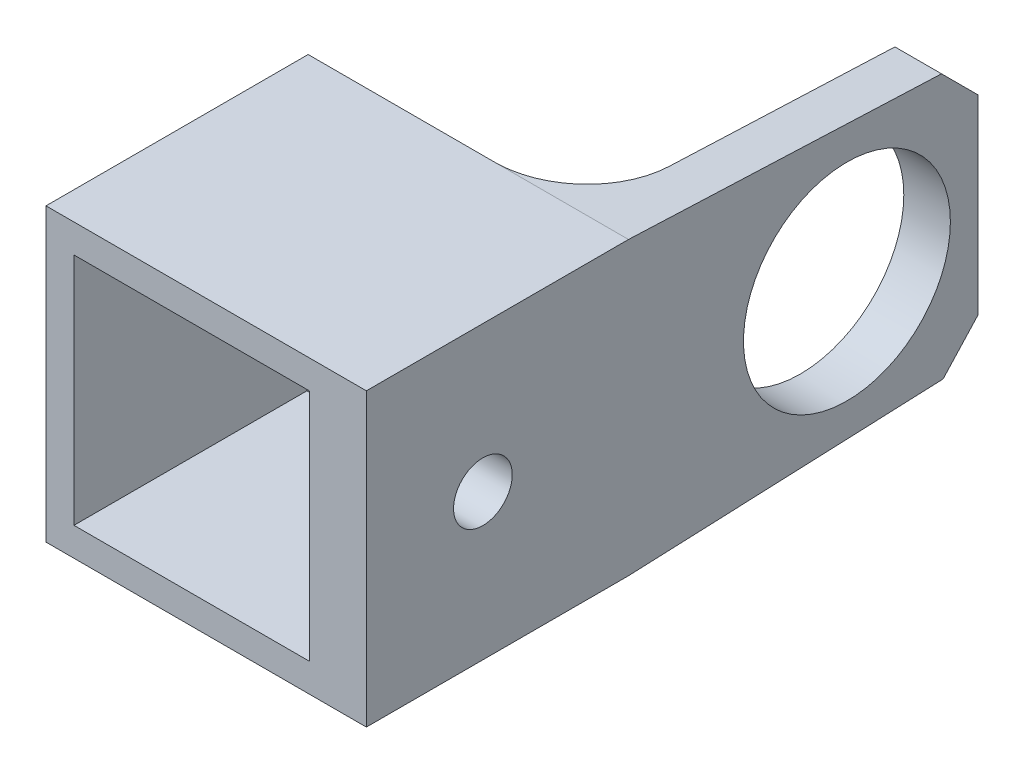
SolidWorks part; units mm, degrees
ref_plane "Front Plane" through (0, 0, 0) normal (0, 0, 1) x (1, 0, 0)
ref_plane "Top Plane" through (0, 0, 0) normal (0, 1, 0) x (1, 0, 0)
ref_plane "Right Plane" through (0, 0, 0) normal (1, 0, 0) x (0, 0, -1)
sketch "Sketch1" plane through (0, 0, 0) normal (0, 0, 1) x (1, 0, 0)
  line L1 (-15.875, -15.875) -> (15.875, -15.875)
  line L2 (-15.875, -15.875) -> (-15.875, 15.875)
  line L3 (-15.875, 15.875) -> (15.875, 15.875)
  line L4 (15.875, -15.875) -> (15.875, 15.875)
  line L5 (-15.875, -15.875) -> (15.875, 15.875) construction
  line L6 (-15.875, 15.875) -> (15.875, -15.875) construction
  point P0 (0, 0)
  dimension "D1" = 31.75
extrude "Boss-Extrude1" add sketch "Sketch1" along normal blind 28.575
sketch "Sketch2" plane through (0, 0, 28.575) normal (0, 0, 1) x (1, 0, 0)
  line L1 (-12.827, -12.7635) -> (12.827, -12.7635)
  line L2 (-12.827, -12.7635) -> (-12.827, 12.7635)
  line L3 (-12.827, 12.7635) -> (12.827, 12.7635)
  line L4 (12.827, -12.7635) -> (12.827, 12.7635)
  line L5 (-12.827, -12.7635) -> (12.827, 12.7635) construction
  line L6 (-12.827, 12.7635) -> (12.827, -12.7635) construction
  point P0 (0, 0)
  dimension "D1" = 25.654
  dimension "D2" = 25.527
extrude "Cut-Extrude1" cut sketch "Sketch2" against normal blind 25.4
sketch "Sketch4" plane through (15.875, 0, 0) normal (1, 0, 0) x (0, 0, -1)
  line L0 (-28.575, -15.875) -> (0, -15.875) construction
  line L1 (-28.575, -15.875) -> (-28.575, 15.875) construction
  line L2 (-28.575, 15.875) -> (0, 15.875) construction
  line L3 (-28.575, -15.875) -> (0, -15.875)
  line L4 (-28.575, -15.875) -> (-28.575, 15.875)
  line L5 (-28.575, 15.875) -> (0, 15.875)
  line L6 (0, 15.875) -> (38.1, 14.2875)
  line L7 (38.1, 14.2875) -> (38.1, -14.2875)
  line L8 (38.1, -14.2875) -> (0, -15.875)
  point P6 (38.1, -14.9469)
  dimension "D1" = 28.575
  dimension "D2" = 38.1
extrude "Boss-Extrude2" add sketch "Sketch4" along normal blind 3.175
sketch "Sketch5" plane through (15.875, 0, 0) normal (-1, 0, 0) x (0, 0, 1)
  line L4 (-38.1, -14.2875) -> (0, -15.875)
  line L5 (0, -15.875) -> (0, 15.875)
  line L6 (0, 15.875) -> (-38.1, 14.2875)
  line L7 (-38.1, 14.2875) -> (-38.1, -14.2875)
  line L8 (-38.1, -14.2875) -> (0, -15.875)
  line L9 (0, -15.875) -> (0, 15.875)
  line L10 (0, 15.875) -> (-38.1, 14.2875)
  line L11 (-38.1, 14.2875) -> (-38.1, -14.2875)
  dimension "D1" = 0
extrude "Boss-Extrude3" add sketch "Sketch5" along normal blind 1.905
fillet "Fillet1" radius 9.525 1 edges at (13.97, 0, 0)
sketch "Sketch6" plane through (19.05, 0, 0) normal (1, 0, 0) x (0, 0, -1)
  line L0 (-28.575, 15.875) -> (-28.575, -15.875) construction
  line L4 (9.525, -15.4781) -> (38.1, -14.2875)
  line L5 (9.525, 15.4781) -> (9.525, -15.4781)
  line L6 (38.1, 14.2875) -> (9.525, 15.4781)
  line L7 (38.1, -14.2875) -> (38.1, 14.2875)
  line L8 (9.525, -15.4781) -> (38.1, -14.2875) construction
  line L9 (9.525, 15.4781) -> (9.525, -15.4781) construction
  line L10 (38.1, 14.2875) -> (9.525, 15.4781) construction
  line L11 (38.1, -14.2875) -> (38.1, 14.2875) construction
  circle A0 centre (23.8125, 0) radius 11.2776
  circle A1 centre (-15.875, 0) radius 3.2004
  point P2 (9.525, 0)
  point P4 (23.8125, 14.8828)
  dimension "D2" = 22.5552
  dimension "D3" = 6.4008
  dimension "D4" = 12.7
  dimension "D1" = 0
extrude "Cut-Extrude2" cut sketch "Sketch6" against normal up to next
chamfer "Chamfer1" distance 3.81 angle 45 2 edges at (16.51, -14.2875, -38.1) (16.51, 14.2875, -38.1)
